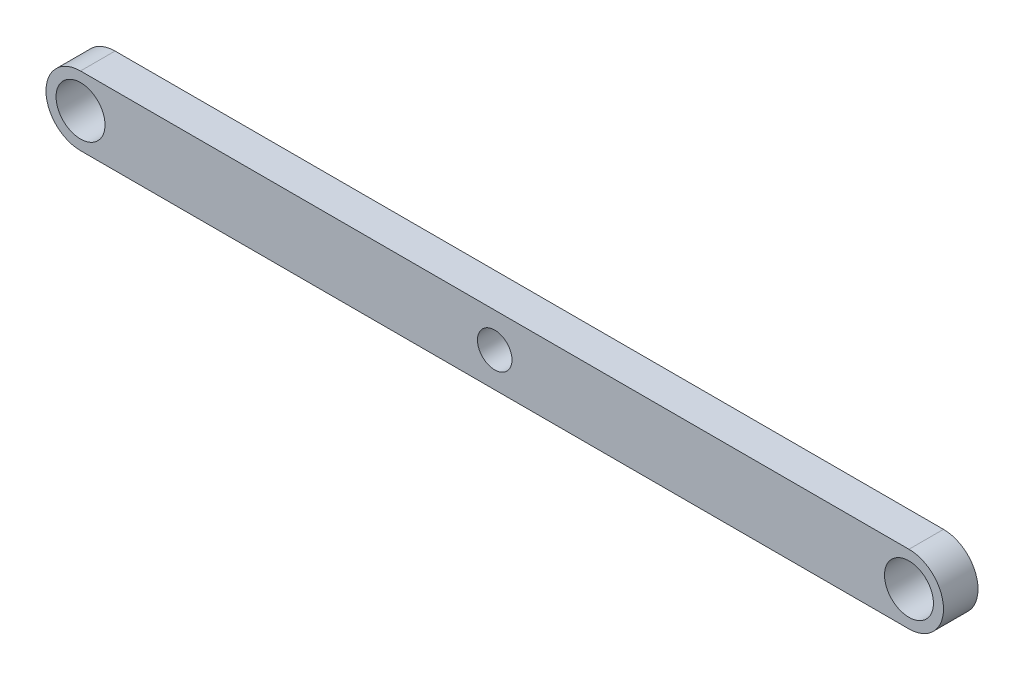
SolidWorks part; units mm, degrees
ref_plane "Front Plane" through (0, 0, 0) normal (0, 0, 1) x (1, 0, 0)
ref_plane "Top Plane" through (0, 0, 0) normal (0, 1, 0) x (1, 0, 0)
ref_plane "Right Plane" through (0, 0, 0) normal (1, 0, 0) x (0, 0, -1)
sketch "Sketch1" plane through (0, 0, 0) normal (0, 0, 1) x (1, 0, 0)
  line L0 (-76.2, 0) -> (76.2, 0) construction
  line L1 (-76.2, 6.35) -> (76.2, 6.35)
  line L2 (-76.2, -6.35) -> (76.2, -6.35)
  arc A0 (-76.2, 6.35) -> (-76.2, -6.35) centre (-76.2, 0) ccw
  arc A1 (76.2, -6.35) -> (76.2, 6.35) centre (76.2, 0) ccw
  circle A2 centre (-76.2, 0) radius 4.5
  circle A3 centre (76.2, 0) radius 4.5
  circle A4 centre (0, 0) radius 3.175
  point P2 (0, 0)
  dimension "D3" = 9
  dimension "D4" = 6.35
  dimension "D1" = 152.4
  dimension "D2" = 12.7
extrude "Boss-Extrude1" add sketch "Sketch1" along normal blind 6.35 contours A2 | A2 region at (0, 4.6941, 0)
